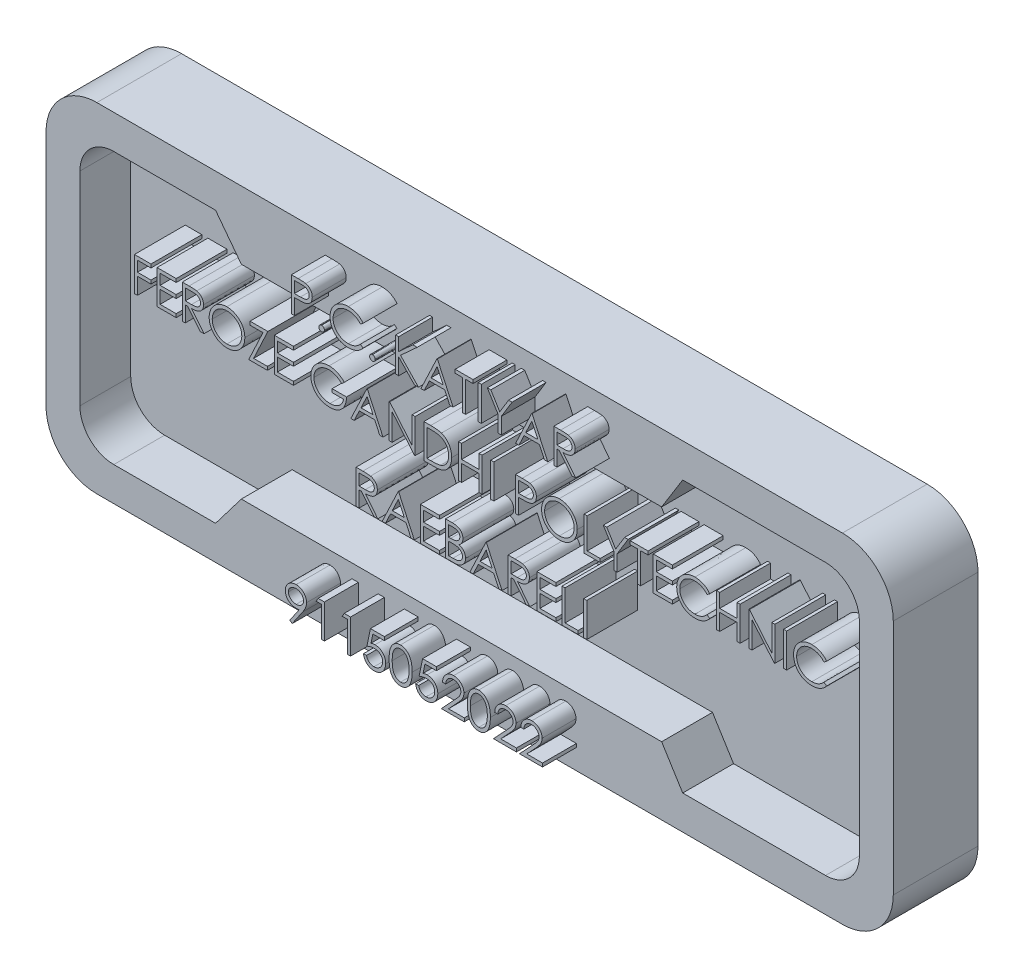
SolidWorks part; units mm, degrees
ref_plane "Front Plane" through (0, 0, 0) normal (0, 0, 1) x (1, 0, 0)
ref_plane "Top Plane" through (0, 0, 0) normal (0, 1, 0) x (1, 0, 0)
ref_plane "Right Plane" through (0, 0, 0) normal (1, 0, 0) x (0, 0, -1)
sketch "Sketch1" plane through (0, 0, 0) normal (0, 0, 1) x (1, 0, 0)
  line L1 (-22, -10) -> (22, -10)
  line L2 (-25, -7) -> (-25, 7)
  line L3 (-22, 10) -> (22, 10)
  line L4 (25, -7) -> (25, 7)
  line L5 (-25, -10) -> (25, 10) construction
  line L6 (-25, 10) -> (25, -10) construction
  arc A0 (25, -7) -> (22, -10) centre (22, -7) cw
  arc A1 (-25, -7) -> (-22, -10) centre (-22, -7) ccw
  arc A2 (25, 7) -> (22, 10) centre (22, 7) ccw
  arc A3 (-22, 10) -> (-25, 7) centre (-22, 7) ccw
  point P0 (0, 0)
  dimension "D3" = 3
  dimension "D1" = 50
  dimension "D2" = 20
extrude "Boss-Extrude1" add sketch "Sketch1" along normal blind 5
sketch "Sketch3" plane through (0, 0, 5) normal (0, 0, 1) x (1, 0, 0)
  line L0 (-25, 7) -> (-25, -7) construction
  line L1 (-21, -8) -> (21, -8)
  line L2 (-23, -6) -> (-23, 6)
  line L3 (-21, 8) -> (-14.9927, 8)
  line L4 (23, -6) -> (23, 6)
  line L5 (-23, -8) -> (23, 8) construction
  line L6 (-23, 8) -> (23, -8) construction
  line L7 (25, -7) -> (25, 7) construction
  line L8 (22, 10) -> (-22, 10) construction
  line L9 (-22, -10) -> (22, -10) construction
  line L14 (-14.9927, 8) -> (-13.4727, 6)
  line L15 (-13.4727, 6) -> (11.3309, 6)
  line L16 (11.3309, 6) -> (12.5745, 8)
  line L17 (-14.9927, -8) -> (-13.4727, -6)
  line L18 (12.5745, -8) -> (11.3309, -6)
  line L19 (12.5745, 8) -> (21, 8)
  line L22 (-13.4727, -6) -> (11.3309, -6)
  arc A0 (-21, -8) -> (-23, -6) centre (-21, -6) cw
  arc A1 (23, -6) -> (21, -8) centre (21, -6) cw
  arc A2 (23, 6) -> (21, 8) centre (21, 6) ccw
  arc A3 (-21, 8) -> (-23, 6) centre (-21, 6) ccw
  point P0 (0, 0)
  point P14 (-21, 6)
  point P15 (21, 6)
  point P16 (21, -6)
  point P17 (-21, -6)
  dimension "D5" = 2
  dimension "D1" = 2
  dimension "D2" = 2
  dimension "D3" = 2
  dimension "D4" = 2
extrude "Cut-Extrude2" cut sketch "Sketch3" against normal blind 3 contours L3 A3 L2 A0 L1 L17 L22 L18 A1 L4 A2 L19 L16 L15 L14 region at (0.1904, 0, 5)
sketch "Sketch4" plane through (0, 0, 5) normal (0, 0, 1) x (1, 0, 0)
  text T0 "P.C. KATIYAR" font "Century Gothic" height 2
  text T1 "9115052022" font "Century Gothic" height 2
extrude "Boss-Extrude2" add sketch "Sketch4" along normal blind 2
sketch "Sketch6" plane through (0, 0, 2) normal (0, 0, 1) x (1, 0, 0)
  circle A0 centre (-21.983, 0) radius 0.75
  dimension "D1" = 1.5
extrude "Cut-Extrude3" cut sketch "Sketch6" against normal blind 2
sketch "Sketch9" plane through (0, 0, 2) normal (0, 0, 1) x (1, 0, 0)
  text T0 "FEROZE GANDHI POLYTECHNIC\r\n                 RAEBARELI" font "Century Gothic" height 2
extrude "Boss-Extrude3" add sketch "Sketch9" along normal blind 3
